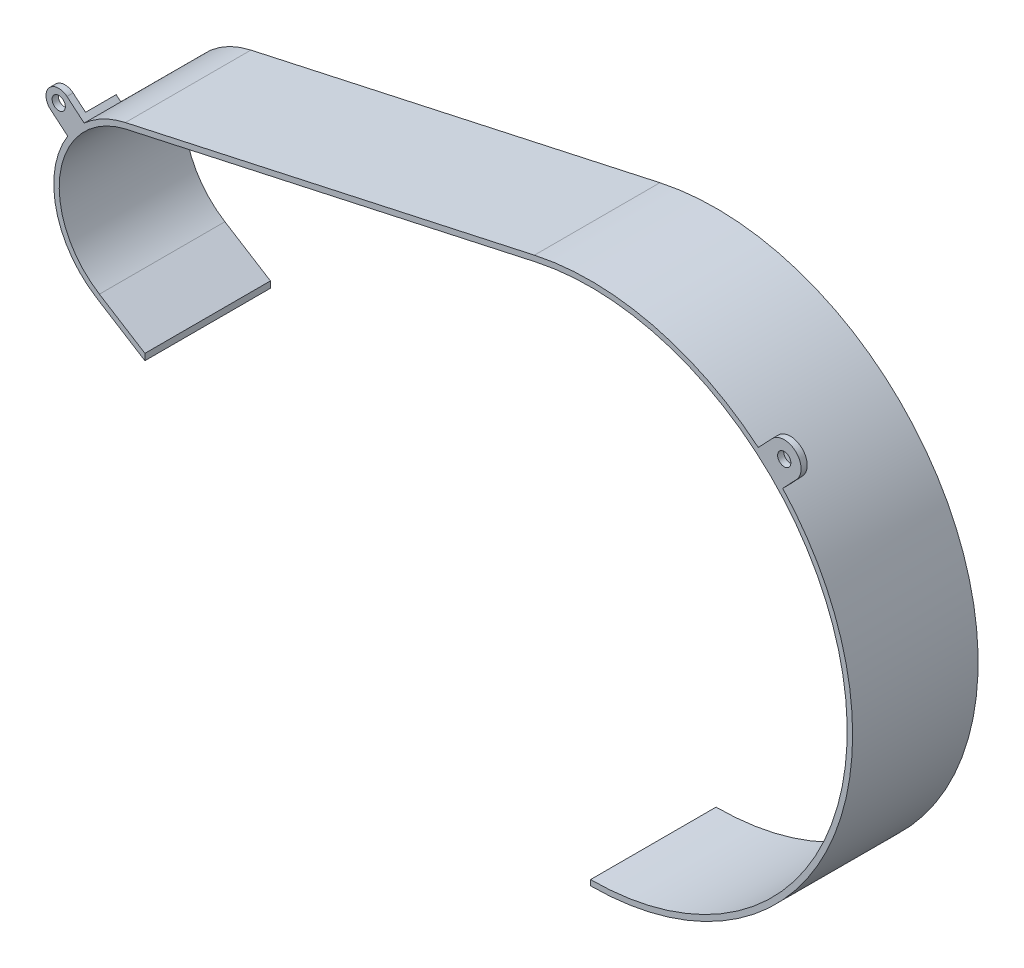
SolidWorks part; units mm, degrees
ref_plane "Front Plane" through (0, 0, 0) normal (0, 0, 1) x (1, 0, 0)
ref_plane "Top Plane" through (0, 0, 0) normal (0, 1, 0) x (1, 0, 0)
ref_plane "Right Plane" through (0, 0, 0) normal (1, 0, 0) x (0, 0, -1)
ref_plane "Plane1" through (0, 0, 61.5) normal (0, 0, 1) x (1, 0, 0)
ref_plane "Plane2" through (0, 0, 30.75) normal (0, 0, 1) x (1, 0, 0)
sketch "Sketch1" plane through (0, 0, 0) normal (0, 0, 1) x (1, 0, 0)
  line L0 (-6.8606, 95.0043) -> (191.7043, 141.5831) construction
  line L1 (-15.3604, 46.0483) -> (155.8828, -64.737) construction
  line L2 (-22.9887, 33.1233) -> (150.9206, -75.8029)
  line L3 (190.7626, 153.674) -> (-9.6857, 109.7441)
  line L4 (190.1932, 156.2724) -> (-10.2551, 112.3424)
  line L5 (-24.4006, 30.869) -> (149.5086, -78.0572)
  circle A0 centre (-0.6944, 68.7178) radius 27 construction
  circle A1 centre (217.6911, 30.8015) radius 113.7887 construction
  arc A2 (-9.6857, 109.7441) -> (-22.9887, 33.1233) centre (-0.6944, 68.7178) ccw
  arc A3 (150.9206, -75.8029) -> (190.7626, 153.674) centre (217.6911, 30.8015) ccw
  arc A4 (-10.2551, 112.3424) -> (-24.4006, 30.869) centre (-0.6944, 68.7178) ccw
  arc A5 (149.5086, -78.0572) -> (190.1932, 156.2724) centre (217.6911, 30.8015) ccw
  circle A6 centre (-0.6944, 68.7178) radius 27 construction
  arc A7 (156.4331, -65.0907) -> (192.3416, 141.7306) centre (217.6911, 30.8015) ccw construction
  dimension "D5" = 15
  dimension "D6" = 12
  dimension "D7" = 2.66
extrude "Boss-Extrude2" add sketch "Sketch1" along normal up to surface (61.5 mm away) up to plane "Plane1"
sketch "Sketch2" plane through (0, 0, 61.5) normal (0, 0, 1) x (1, 0, 0)
  line L1 (217.6911, -97.6472) -> (-0.6944, -97.6472)
  line L2 (217.6911, -97.6472) -> (217.6911, 26.7178)
  line L3 (217.6911, 26.7178) -> (-0.6944, 26.7178)
  line L4 (-0.6944, -97.6472) -> (-0.6944, 26.7178)
  line L5 (217.6911, -97.6472) -> (-0.6944, 26.7178) construction
  line L6 (217.6911, 26.7178) -> (-0.6944, -97.6472) construction
  circle A0 centre (-0.6944, 68.7178) radius 42 construction
  arc A1 (-9.6857, 109.7441) -> (-22.9887, 33.1233) centre (-0.6944, 68.7178) ccw construction
  circle A2 centre (217.6911, 30.8015) radius 125.7887 construction
  arc A3 (150.9206, -75.8029) -> (190.7626, 153.674) centre (217.6911, 30.8015) ccw construction
  arc A5 (149.5086, -78.0572) -> (190.1932, 156.2724) centre (217.6911, 30.8015) ccw construction
  point P12 (108.4984, -35.4647)
  point P17 (-0.6944, 26.7178)
  point P28 (217.6911, -94.9872)
extrude "Cut-Extrude1" cut sketch "Sketch2" against normal through all contours L1 L2 L3 L4 | L2 L1 | L1 L2 region at (108.4984, -35.4647, 61.5)
ref_plane "Plane3" through (0, 68.7178, 0) normal (0, -1, 0) x (-1, 0, 0)
sketch "Sketch3" plane through (0, 0, 61.5) normal (0, 0, 1) x (1, 0, 0)
  line L0 (-42.9202, 104.2985) -> (-31.6801, 60.7249) construction
  line L1 (-31.6801, 60.7249) -> (-42.9202, 104.2985) construction
  line L2 (-46.9475, 99.519) -> (-38.5378, 92.4327)
  line L3 (-38.8929, 109.078) -> (-30.4831, 101.9917)
  line L4 (-38.5378, 92.4327) -> (-30.4831, 101.9917) construction
  line L5 (-55, 68.7178) -> (55, 68.7178) construction
  circle A0 centre (-0.6944, 68.7178) radius 32 construction
  circle A1 centre (-42.9202, 104.2985) radius 3.25
  arc A2 (-46.9475, 99.519) -> (-38.8929, 109.078) centre (-42.9202, 104.2985) cw
  arc A3 (-10.2551, 112.3424) -> (-24.4006, 30.869) centre (-0.6944, 68.7178) ccw construction
  arc A4 (-30.4831, 101.9917) -> (-38.5378, 92.4327) centre (-0.6944, 68.7178) ccw
  circle A9 centre (-42.9202, 104.2985) radius 3.25 construction
  point P6 (-32.6944, 68.7178)
  dimension "D1" = 64
  dimension "D2" = 6.5
  dimension "D3" = 3
extrude "Boss-Extrude3" add sketch "Sketch3" against normal blind 3
sketch "Sketch5" plane through (0, 0, 58.5) normal (0, 0, -1) x (-1, 0, 0)
  line L0 (32.7773, 103.9248) -> (40.8319, 94.3659)
  line L1 (30.4831, 101.9917) -> (38.8929, 109.078) construction
  line L2 (46.9475, 99.519) -> (38.5378, 92.4327) construction
  line L3 (32.7773, 103.9248) -> (30.4831, 101.9917)
  line L4 (30.4831, 101.9917) -> (38.5378, 92.4327)
  line L5 (38.5378, 92.4327) -> (40.8319, 94.3659)
  dimension "D1" = 3
extrude "Boss-Extrude4" add sketch "Sketch5" along normal blind 15
sketch "Sketch6" plane through (0, 0, 61.5) normal (0, 0, 1) x (1, 0, 0)
  line L0 (306.6284, 136.5963) -> (299.8985, 129.4981)
  line L1 (318.6022, 125.2438) -> (311.8723, 118.1456)
  line L2 (299.8985, 129.4981) -> (311.8723, 118.1456) construction
  line L3 (312.6153, 130.9201) -> (346.3704, 130.9201) construction
  circle A0 centre (312.6153, 130.9201) radius 3.25
  circle A1 centre (-42.9202, 104.2985) radius 3.25 construction
  arc A2 (306.6284, 136.5963) -> (318.6022, 125.2438) centre (312.6153, 130.9201) cw
  arc A3 (149.5086, -78.0572) -> (190.1932, 156.2724) centre (217.6911, 30.8015) ccw construction
  arc A4 (299.8985, 129.4981) -> (311.8723, 118.1456) centre (217.6911, 30.8015) cw
  dimension "D1" = 5
extrude "Boss-Extrude5" add sketch "Sketch6" against normal blind 3
